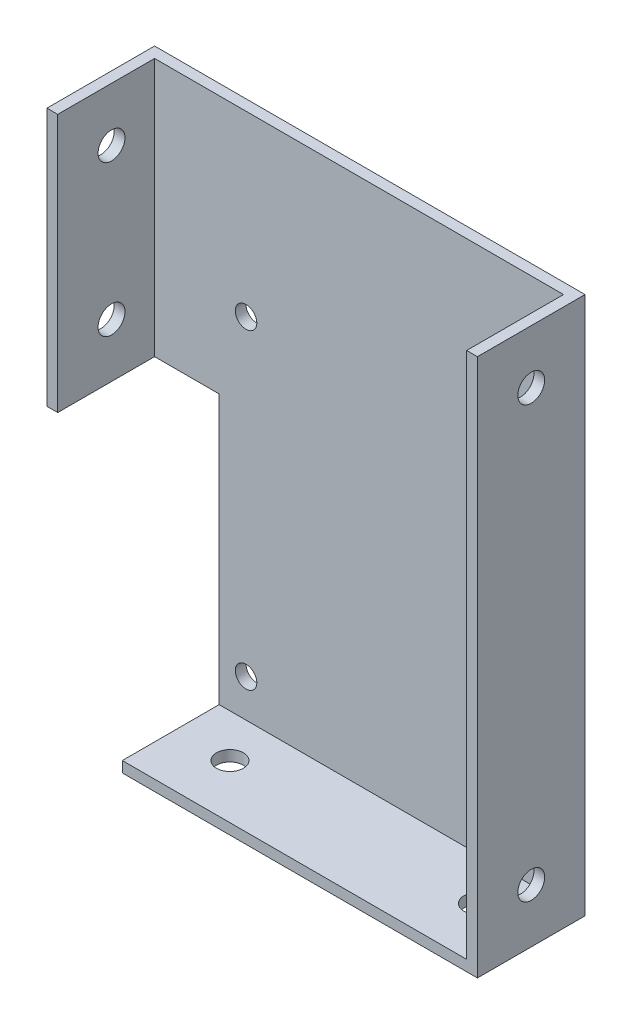
SolidWorks part; units mm, degrees
ref_plane "Alzado" through (0, 0, 0) normal (0, 0, 1) x (1, 0, 0)
ref_plane "Planta" through (0, 0, 0) normal (0, 1, 0) x (1, 0, 0)
ref_plane "Vista lateral" through (0, 0, 0) normal (1, 0, 0) x (0, 0, -1)
sketch "Sketch1" plane through (0, 0, 0) normal (0, 0, 1) x (1, 0, 0)
  line L1 (-15.7576, 19.8268) -> (24.2424, 19.8268)
  line L2 (-15.7576, 19.8268) -> (-15.7576, -30.1732)
  line L3 (-15.7576, -30.1732) -> (24.2424, -30.1732)
  line L4 (24.2424, 19.8268) -> (24.2424, -30.1732)
  dimension "D1" = 40
  dimension "D2" = 50
extrude "Boss-Extrude1" add sketch "Sketch1" along normal blind 1
sketch "Sketch2" plane through (0, 0, 1) normal (0, 0, 1) x (1, 0, 0)
  line L1 (-15.7576, -30.1732) -> (-10.7576, -30.1732)
  line L2 (-15.7576, -30.1732) -> (-15.7576, -5.1732)
  line L3 (-15.7576, -5.1732) -> (-10.7576, -5.1732)
  line L4 (-10.7576, -30.1732) -> (-10.7576, -5.1732)
  dimension "D1" = 5
  dimension "D2" = 25
extrude "Cut-Extrude1" cut sketch "Sketch2" against normal blind 1
sketch "Sketch3" plane through (0, 0, 0) normal (0, 0, -1) x (-1, 0, 0)
  line L0 (10.7576, -5.1732) -> (15.7576, -5.1732) construction
  line L1 (15.7576, 19.8268) -> (14.7576, 19.8268)
  line L2 (15.7576, 19.8268) -> (15.7576, -5.1732)
  line L3 (15.7576, -5.1732) -> (14.7576, -5.1732)
  line L4 (14.7576, 19.8268) -> (14.7576, -5.1732)
  line L6 (-24.2424, 19.8268) -> (-23.2424, 19.8268)
  line L7 (-24.2424, 19.8268) -> (-24.2424, -5.1732)
  line L8 (-24.2424, -5.1732) -> (-23.2424, -5.1732)
  line L9 (-23.2424, 19.8268) -> (-23.2424, -5.1732)
  dimension "D1" = 1
  dimension "D2" = 1
extrude "Boss-Extrude2" add sketch "Sketch3" against normal blind 10
sketch "Sketch4" plane through (24.2424, 0, 0) normal (1, 0, 0) x (0, 0, -1)
  line L0 (-10, 19.8268) -> (-10, -5.1732) construction
  line L1 (-10, -5.1732) -> (-1, -5.1732) construction
  line L2 (-10, 19.8268) -> (0, 19.8268) construction
  circle A0 centre (-5, -0.1732) radius 1.25
  circle A1 centre (-5, 14.8268) radius 1.25
  dimension "D1" = 2.5
  dimension "D4" = 2.5
  dimension "D2" = 5
  dimension "D3" = 5
  dimension "5" = 5
extrude "Cut-Extrude3" cut sketch "Sketch4" against normal blind 63
sketch "Sketch5" plane through (24.2424, 0, 0) normal (1, 0, 0) x (0, 0, -1)
  circle A0 centre (-5, -0.1732) radius 1.25
extrude "Boss-Extrude3" add sketch "Sketch5" against normal blind 1
sketch "Sketch6" plane through (0, 0, 10) normal (0, 0, 1) x (1, 0, 0)
  line L0 (-15.7576, -5.1732) -> (-15.7576, 19.8268) construction
  line L1 (24.2424, -5.1732) -> (-15.7576, -5.1732)
  line L2 (24.2424, -5.1732) -> (24.2424, 4.8268)
  line L3 (24.2424, 4.8268) -> (-15.7576, 4.8268)
  line L4 (-15.7576, -5.1732) -> (-15.7576, 4.8268)
  dimension "D1" = 10
extrude "Cut-Extrude4" cut sketch "Sketch6" against normal blind 9
sketch "Sketch7" plane through (-15.7576, 0, 0) normal (-1, 0, 0) x (0, 0, 1)
  line L0 (1, 4.8268) -> (10, 4.8268) construction
  circle A0 centre (5, 9.8268) radius 1.25
  dimension "D1" = 2.5
  dimension "D2" = 5
extrude "Cut-Extrude5" cut sketch "Sketch7" against normal blind 53
sketch "Sketch8" plane through (0, 0, 1) normal (0, 0, 1) x (1, 0, 0)
  line L0 (-10.7576, -30.1732) -> (24.2424, -30.1732) construction
  line L1 (-10.7576, -5.1732) -> (-8.7576, -5.1732)
  line L2 (-10.7576, -5.1732) -> (-10.7576, -30.1732)
  line L3 (-10.7576, -30.1732) -> (-8.7576, -30.1732)
  line L4 (-8.7576, -5.1732) -> (-8.7576, -30.1732)
  dimension "D1" = 2
extrude "Cut-Extrude6" cut sketch "Sketch8" against normal blind 53
sketch "Sketch9" plane through (0, 0, 1) normal (0, 0, 1) x (1, 0, 0)
  line L0 (-8.7576, -30.1732) -> (-8.7576, -5.1732) construction
  line L1 (-15.7576, -5.1732) -> (-8.7576, -5.1732)
  line L2 (-15.7576, -5.1732) -> (-15.7576, -3.1732)
  line L3 (-15.7576, -3.1732) -> (-8.7576, -3.1732)
  line L4 (-8.7576, -5.1732) -> (-8.7576, -3.1732)
  dimension "D1" = 2
extrude "Cut-Extrude8" cut sketch "Sketch9" against normal blind 53
sketch "Sketch10" plane through (24.2424, 0, 0) normal (1, 0, 0) x (0, 0, -1)
  line L0 (-1, -30.1732) -> (-1, 4.8268) construction
  line L1 (-10, 4.8268) -> (-1, 4.8268)
  line L2 (-10, 4.8268) -> (-10, -15.8236)
  line L3 (-10, -15.8236) -> (-1, -15.8236)
  line L4 (-1, 4.8268) -> (-1, -15.8236)
extrude "Boss-Extrude4" add sketch "Sketch10" against normal blind 1
sketch "Sketch11" plane through (24.2424, 0, 0) normal (1, 0, 0) x (0, 0, -1)
  line L0 (-10, -15.8236) -> (-1, -15.8236) construction
  line L1 (0, -30.1732) -> (0, 19.8268) construction
  circle A0 centre (-5, -10.8236) radius 1.25
  dimension "D1" = 5
  dimension "D2" = 5
extrude "Cut-Extrude9" cut sketch "Sketch11" against normal blind 1
sketch "Sketch12" plane through (24.2424, 0, 0) normal (1, 0, 0) x (0, 0, -1)
  circle A0 centre (-5, 9.8268) radius 1.25
extrude "Boss-Extrude5" add sketch "Sketch12" against normal blind 1
sketch "Sketch13" plane through (-15.7576, 0, 0) normal (-1, 0, 0) x (0, 0, 1)
  circle A0 centre (5, 9.8268) radius 1.25
extrude "Boss-Extrude6" add sketch "Sketch13" against normal blind 1
sketch "Sketch14" plane through (0, 0, 1) normal (0, 0, 1) x (1, 0, 0)
  line L0 (-8.7576, -30.1732) -> (-8.7576, -3.1732) construction
  line L1 (-15.7576, -3.1732) -> (-8.7576, -3.1732)
  line L2 (-15.7576, -3.1732) -> (-15.7576, -4.1732)
  line L3 (-15.7576, -4.1732) -> (-8.7576, -4.1732)
  line L4 (-8.7576, -3.1732) -> (-8.7576, -4.1732)
  dimension "D1" = 1
extrude "Boss-Extrude7" add sketch "Sketch14" against normal blind 1
sketch "Sketch15" plane through (0, 0, 1) normal (0, 0, 1) x (1, 0, 0)
  line L1 (-15.7576, -4.1732) -> (-14.7576, -4.1732)
  line L2 (-15.7576, -4.1732) -> (-15.7576, 4.8268)
  line L3 (-15.7576, 4.8268) -> (-14.7576, 4.8268)
  line L4 (-14.7576, -4.1732) -> (-14.7576, 4.8268)
extrude "Boss-Extrude8" add sketch "Sketch15" along normal blind 9
sketch "Sketch16" plane through (-15.7576, 0, 0) normal (-1, 0, 0) x (0, 0, 1)
  line L0 (0, -4.1732) -> (10, -4.1732) construction
  circle A0 centre (5, 14.8268) radius 1.25
  circle A1 centre (5, 0.8268) radius 1.25
  dimension "D1" = 5
extrude "Cut-Extrude10" cut sketch "Sketch16" against normal blind 9
sketch "Sketch17" plane through (0, 0, 1) normal (0, 0, 1) x (1, 0, 0)
  line L0 (23.2424, -15.8236) -> (23.2424, 19.8268) construction
  line L1 (24.2424, -30.1732) -> (23.2424, -30.1732)
  line L2 (24.2424, -30.1732) -> (24.2424, 1.2337)
  line L3 (24.2424, 1.2337) -> (23.2424, 1.2337)
  line L4 (23.2424, -30.1732) -> (23.2424, 1.2337)
extrude "Boss-Extrude9" add sketch "Sketch17" along normal blind 9
sketch "Sketch18" plane through (24.2424, 0, 0) normal (1, 0, 0) x (0, 0, -1)
  line L0 (-10, -30.1732) -> (0, -30.1732) construction
  circle A1 centre (-5, -25.1732) radius 1.25
  dimension "D1" = 5
extrude "Cut-Extrude11" cut sketch "Sketch18" against normal blind 9
sketch "Sketch19" plane through (0, 0, 1) normal (0, 0, 1) x (1, 0, 0)
  line L0 (24.2424, 19.8268) -> (24.2424, -30.1732) construction
  line L1 (-8.7576, -30.1732) -> (24.2424, -30.1732)
  line L2 (-8.7576, -30.1732) -> (-8.7576, -29.1732)
  line L3 (-8.7576, -29.1732) -> (24.2424, -29.1732)
  line L4 (24.2424, -30.1732) -> (24.2424, -29.1732)
  dimension "D1" = 1
extrude "Boss-Extrude10" add sketch "Sketch19" along normal blind 9
sketch "Sketch20" plane through (0, -30.1732, 0) normal (0, -1, 0) x (1, 0, 0)
  line L0 (-8.7576, 0) -> (24.2424, 0) construction
  line L1 (-8.7576, 0) -> (-8.7576, 10) construction
  line L2 (24.2424, 10) -> (24.2424, 0) construction
  circle A0 centre (-3.7576, 5) radius 1.25
  circle A1 centre (19.2424, 5) radius 1.25
  dimension "D1" = 5
  dimension "D3" = 5
  dimension "D2" = 5
extrude "Cut-Extrude12" cut sketch "Sketch20" against normal blind 9
sketch "Sketch21" plane through (0, 0, 0) normal (0, 0, -1) x (-1, 0, 0)
  circle A0 centre (-21.7424, 3.3268) radius 1
  circle A1 centre (6.2576, 3.2785) radius 1
  circle A2 centre (6.2576, -25.6732) radius 1
  circle A3 centre (-21.7424, -25.6732) radius 1
  point P4 (-7.7424, -11.1732)
extrude "Cut-Extrude13" cut sketch "Sketch21" against normal blind 10
